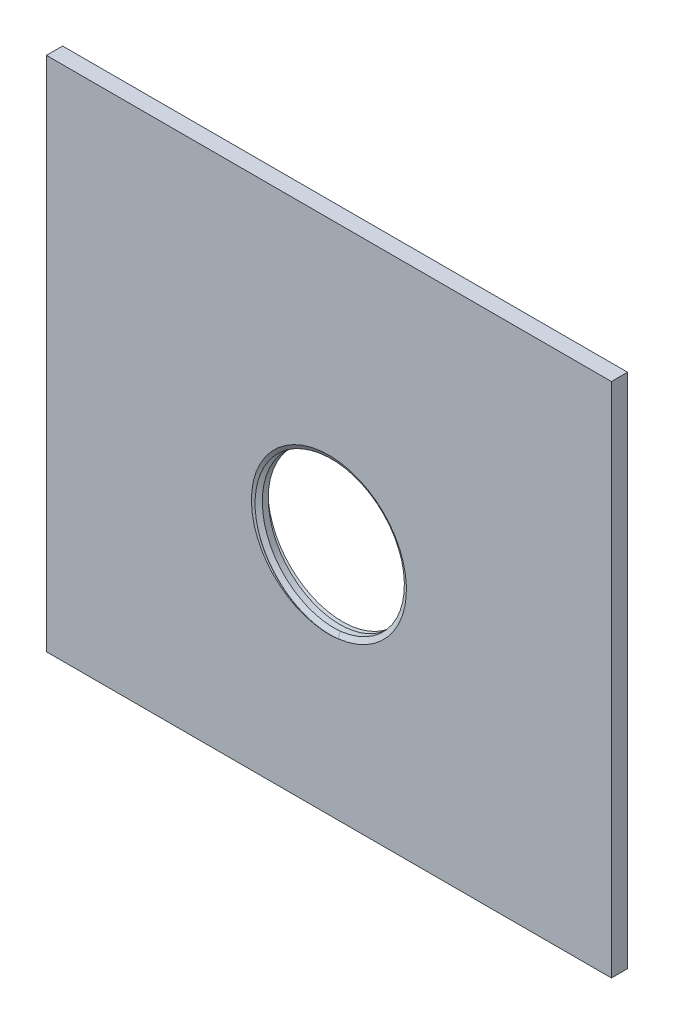
SolidWorks part; units mm, degrees
ref_plane "Front Plane" through (0, 0, 0) normal (0, 0, 1) x (1, 0, 0)
ref_plane "Top Plane" through (0, 0, 0) normal (0, 1, 0) x (1, 0, 0)
ref_plane "Right Plane" through (0, 0, 0) normal (1, 0, 0) x (0, 0, -1)
sketch "Sketch1" plane through (0, 0, 0) normal (0, 0, 1) x (1, 0, 0)
  line L1 (0, 0) -> (35, 0)
  line L2 (0, 0) -> (0, 35)
  line L3 (0, 35) -> (35, 35)
  line L4 (35, 0) -> (35, 35)
  dimension "D1" = 35
  dimension "D2" = 35
extrude "Boss-Extrude1" add sketch "Sketch1" along normal blind 1
sketch "Sketch2" plane through (0, 0, 1) normal (0, 0, 1) x (1, 0, 0)
  circle A0 centre (17.5, 17.5) radius 4.5
  dimension "D1" = 9
extrude "Cut-Extrude1" cut sketch "Sketch2" against normal up to next
sketch "Sketch21" plane through (0, 0, 1) normal (0, 0, 1) x (1, 0, 0)
  circle A0 centre (17.5, 17.5) radius 4.5 construction
  circle A1 centre (17.5, 17.5) radius 4.5
curve "Helix/Spiral8" pitch 0.75 height 2.25 radius 4.5 centre (17.5, 17.5, 1) axis (0, 0, -1) start towards (1, 0, 0)
ref_plane "Plane5" through (0, 17.5, 0) normal (0, -1, 0) x (-1, 0, 0)
sketch "Sketch22" plane through (0, 17.5, 0) normal (0, -1, 0) x (-1, 0, 0)
  line L0 (-35, -1) -> (-35, 0) construction
  line L1 (-22, -1.3822) -> (-22, -1)
  line L2 (-22, -1) -> (-22.301, -1.1738)
  line L3 (-22.301, -1.2084) -> (-22, -1.3822)
  line L4 (-22.2207, -1.1911) -> (-22.2207, -1.2548) construction
  line L5 (-22.2207, -1.1911) -> (-22.2207, -1.1274) construction
  line L7 (-22, -1.1911) -> (-22.311, -1.1911) construction
  circle A0 centre (-22.1103, -1.1911) radius 0.1103 construction
  arc A1 (-22.301, -1.2084) -> (-22.301, -1.1738) centre (-22.291, -1.1911) cw
  dimension "D2" = 0.02
  dimension "D1" = 0.311
sweep "Cut-Sweep9" cut profiles "Sketch22" path "Helix/Spiral8"
sketch "Sketch24" plane through (0, 0, 1) normal (0, 0, 1) x (1, 0, 0)
  circle A0 centre (17.5, 17.5) radius 4.801
extrude "Cut-Extrude2" cut sketch "Sketch24" against normal blind 10 draft 60
sketch "Sketch25" plane through (0, 0, 0) normal (0, 0, -1) x (-1, 0, 0)
  circle A0 centre (-17.5, 17.5) radius 4.801
extrude "Cut-Extrude3" cut sketch "Sketch25" against normal blind 10 draft 60
sketch "Sketch26" plane through (0, 0, 0) normal (0, -1, 0) x (1, 0, 0)
  line L4 (0, 0) -> (35, 0)
  line L5 (35, 0) -> (35, 1)
  line L6 (35, 1) -> (0, 1)
  line L7 (0, 1) -> (0, 0)
  line L8 (0, 0) -> (35, 0)
  line L9 (35, 0) -> (35, 1)
  line L10 (35, 1) -> (0, 1)
  line L11 (0, 1) -> (0, 0)
  dimension "D1" = 0
extrude "Cut-Extrude4" cut sketch "Sketch26" against normal blind 3
